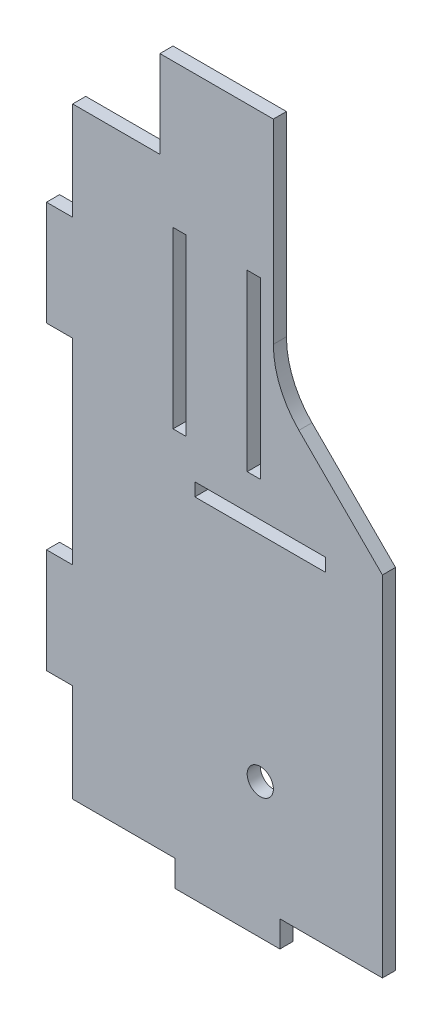
SolidWorks part; units mm, degrees
ref_plane "Front Plane" through (0, 0, 0) normal (0, 0, 1) x (1, 0, 0)
ref_plane "Top Plane" through (0, 0, 0) normal (0, 1, 0) x (1, 0, 0)
ref_plane "Right Plane" through (0, 0, 0) normal (1, 0, 0) x (0, 0, -1)
sketch "Sketch1" plane through (0, 0, 0) normal (0, 0, 1) x (1, 0, 0)
  line L0 (-71, 138) -> (-71, 0)
  line L1 (-71, 0) -> (0, 0)
  line L2 (0, 0) -> (0, 77)
  line L3 (0, 77) -> (-31, 77)
  line L4 (-31, 77) -> (-31, 138)
  line L5 (-31, 138) -> (-71, 138)
  dimension "D1" = 77
  dimension "D2" = 71
  dimension "D3" = 40
  dimension "D4" = 138
extrude "BaseShape" add sketch "Sketch1" along normal blind 3
sketch "Sketch2" plane through (0, 0, 3) normal (0, 0, 1) x (1, 0, 0)
  line L1 (-71, 0) -> (0, 0) construction
  line L2 (0, 0) -> (0, 77) construction
  circle A0 centre (-28, 25) radius 3
  dimension "D1" = 6
  dimension "D2" = 28
  dimension "D3" = 25
extrude "ShaftHoles" cut sketch "Sketch2" against normal through all
sketch "Sketch4" plane through (0, 0, 3) normal (0, 0, 1) x (1, 0, 0)
  line L0 (-31, 77) -> (-31, 138) construction
  line L1 (0, 77) -> (-31, 77)
  line L2 (0, 77) -> (0, 80)
  line L3 (0, 80) -> (-31, 80) construction
  line L4 (-31, 77) -> (-31, 80)
  line L5 (-71, 138) -> (-71, 0) construction
  line L6 (-71, 115.5) -> (-77, 115.5)
  line L7 (-71, 115.5) -> (-71, 91.5)
  line L8 (-71, 91.5) -> (-77, 91.5)
  line L9 (-77, 115.5) -> (-77, 91.5)
  line L10 (-71, 0) -> (0, 0) construction
  line L11 (-71, 46.5) -> (-77, 46.5)
  line L12 (-71, 46.5) -> (-71, 22.5)
  line L13 (-71, 22.5) -> (-77, 22.5)
  line L14 (-77, 46.5) -> (-77, 22.5)
  line L15 (-47.5, 0) -> (-23.5, 0)
  line L16 (-47.5, 0) -> (-47.5, -6)
  line L17 (-47.5, -6) -> (-23.5, -6)
  line L18 (-23.5, 0) -> (-23.5, -6)
  line L19 (-71, 115.5) -> (-71, 138) construction
  line L20 (-71, 22.5) -> (-71, 0) construction
  line L21 (-71, 69) -> (-71, 91.5) construction
  line L22 (-71, 46.5) -> (-71, 69) construction
  line L23 (-71, 0) -> (-71, 69) construction
  line L24 (-47.5, 0) -> (-71, 0) construction
  line L25 (-23.5, 0) -> (0, 0) construction
  line L26 (-25, 80) -> (0, 80)
  line L27 (-31, 138) -> (-25, 138)
  line L28 (-31, 138) -> (-31, 80)
  line L29 (-31, 80) -> (-25, 80) construction
  line L30 (-25, 138) -> (-25, 80)
  point P23 (-71, 69)
  point P28 (-71, 34.5)
  point P32 (-71, 34.5)
  dimension "D1" = 3
  dimension "D2" = 6
  dimension "D3" = 24
  dimension "D4" = 6
extrude "Fingers" add sketch "Sketch4" against normal up to surface (3 mm away) up to face at (-25, 25, 0)
sketch "Sketch5" plane through (0, 0, 3) normal (0, 0, 1) x (1, 0, 0)
  line L0 (0, 0) -> (0, 80) construction
  line L1 (-43, 77) -> (-13, 77)
  line L2 (-43, 77) -> (-43, 74)
  line L3 (-43, 74) -> (-13, 74)
  line L4 (-13, 77) -> (-13, 74)
  line L7 (-48, 125) -> (-45, 125)
  line L8 (-48, 125) -> (-48, 85)
  line L9 (-48, 85) -> (-45, 85)
  line L10 (-45, 125) -> (-45, 85)
  line L11 (0, 80) -> (-25, 80) construction
  line L12 (-25, 80) -> (-25, 138) construction
  line L13 (-31, 125) -> (-28, 125)
  line L14 (-31, 125) -> (-31, 85)
  line L15 (-31, 85) -> (-28, 85)
  line L16 (-28, 125) -> (-28, 85)
  point P20 (-29.5, 85)
  dimension "D1" = 3
  dimension "D2" = 3
  dimension "D3" = 30
  dimension "D4" = 13
  dimension "D5" = 14
  dimension "D6" = 3
  dimension "D7" = 3
  dimension "D8" = 3
  dimension "D9" = 40
  dimension "D10" = 8
extrude "Grooves" cut sketch "Sketch5" against normal through all
chamfer "Chamfer1" distance 25 angle 45 1 edges at (-25, 80, 1.5)
fillet "Fillet2" radius 20 1 edges at (-25, 105, 1.5)
sketch "Sketch6" plane through (0, 138, 0) normal (0, 1, 0) x (1, 0, 0)
  line L0 (-25, -3) -> (-71, -3) construction
  line L1 (-25, 0) -> (-51, 0)
  line L2 (-25, 0) -> (-25, -3)
  line L3 (-25, -3) -> (-51, -3)
  line L4 (-51, 0) -> (-51, -3)
  dimension "D1" = 20
extrude "MarbleChute" add sketch "Sketch6" along normal blind 20
